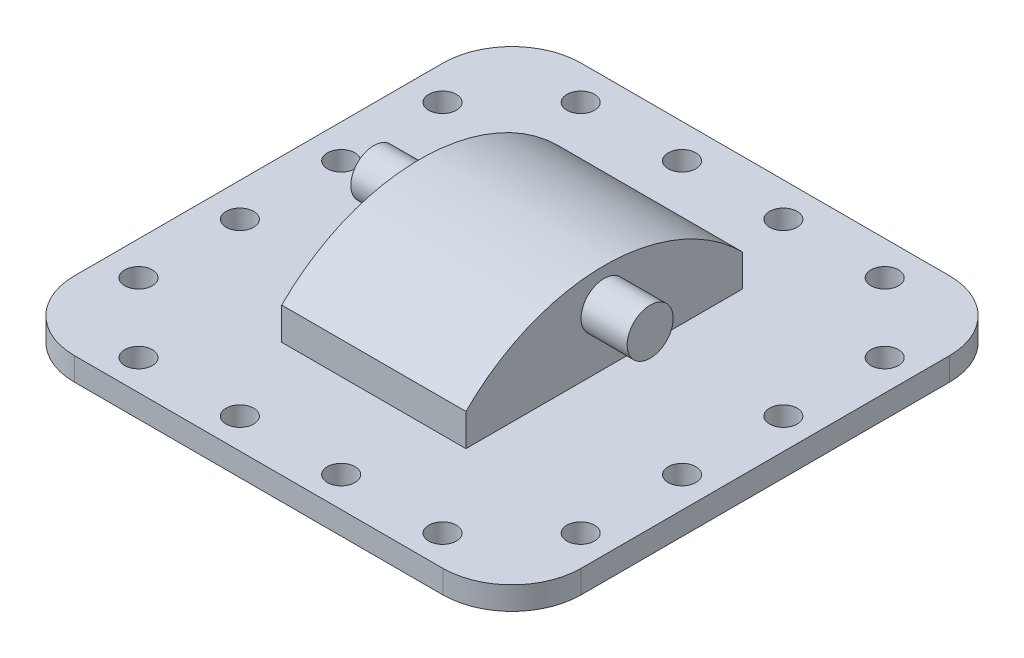
SolidWorks part; units mm, degrees
ref_plane "Front Plane" through (0, 0, 0) normal (0, 0, 1) x (1, 0, 0)
ref_plane "Top Plane" through (0, 0, 0) normal (0, 1, 0) x (1, 0, 0)
ref_plane "Right Plane" through (0, 0, 0) normal (1, 0, 0) x (0, 0, -1)
sketch "Sketch1" plane through (0, 0, 0) normal (0, 1, 0) x (1, 0, 0)
  line L1 (-55, -55) -> (55, -55)
  line L2 (-55, -55) -> (-55, 55)
  line L3 (-55, 55) -> (55, 55)
  line L4 (55, -55) -> (55, 55)
  line L5 (-55, -55) -> (55, 55) construction
  line L6 (-55, 55) -> (55, -55) construction
  point P0 (0, 0)
  dimension "D1" = 110
  dimension "D2" = 110
extrude "Boss-Extrude1" add sketch "Sketch1" along normal blind 5
fillet "Fillet2" radius 15 1 edges at (55, 2.5, -55) type face fillet first side face at (55, 2.5, 0) second side face at (0, 2.5, -55)
fillet "Fillet3" radius 15 1 edges at (-55, 2.5, -55) type face fillet first side face at (-7.5, 2.5, -55) second side face at (-55, 2.5, 0)
fillet "Fillet4" radius 15 1 edges at (-55, 2.5, 55) type face fillet first side face at (-55, 2.5, 7.5) second side face at (0, 2.5, 55)
fillet "Fillet5" radius 15 1 edges at (55, 2.5, 55) type face fillet first side face at (7.5, 2.5, 55) second side face at (55, 2.5, 7.5)
sketch "Sketch2" plane through (0, 5, 0) normal (0, 1, 0) x (1, 0, 0)
  line L1 (-20, -30) -> (20, -30)
  line L2 (-20, -30) -> (-20, 30)
  line L3 (-20, 30) -> (20, 30)
  line L4 (20, -30) -> (20, 30)
  line L5 (-20, -30) -> (20, 30) construction
  line L6 (-20, 30) -> (20, -30) construction
  point P0 (0, 0)
  dimension "D1" = 40
extrude "Boss-Extrude2" add sketch "Sketch2" along normal blind 24
sketch "Sketch4" plane through (20, 0, 0) normal (1, 0, 0) x (0, 0, -1)
  line L0 (-30, 17) -> (30, 17) construction
  line L1 (-30, 29) -> (-30, 5) construction
  line L2 (30, 29) -> (30, 5) construction
  line L3 (0, 17) -> (0, 29) construction
  line L4 (-30, 29) -> (30, 29) construction
  line L5 (0, 29) -> (0, 5) construction
  line L6 (-40, 5) -> (40, 5) construction
  circle A2 centre (0, 17) radius 5
extrude "Boss-Extrude3" add sketch "Sketch4" along normal blind 10 and the other way blind 50
fillet "Fillet6" radius 10 1 edges at (0, 29, 30)
fillet "Fillet7" radius 10 1 edges at (0, 29, -30)
sketch "Sketch5" plane through (0, 0, 0) normal (0, -1, 0) x (1, 0, 0)
  line L0 (55.3347, -39.5816) -> (55.3347, 40.4184)
  line L1 (40.3347, 55.4184) -> (-39.6653, 55.4184)
  line L2 (-54.6653, 40.4184) -> (-54.6653, -39.5816)
  line L3 (-39.6653, -54.5816) -> (40.3347, -54.5816)
  circle A0 centre (48.3347, -10.5816) radius 3
  circle A1 centre (48.3347, 33.4184) radius 3
  circle A2 centre (-47.6653, 11.4184) radius 3
  circle A3 centre (-47.6653, -10.5816) radius 3
  circle A4 centre (-47.6653, -32.5816) radius 3
  circle A5 centre (-32.6653, -47.5816) radius 3
  circle A6 centre (-10.6653, -47.5816) radius 3
  circle A7 centre (11.3347, -47.5816) radius 3
  circle A8 centre (33.3347, -47.5816) radius 3
  circle A9 centre (48.3347, -32.5816) radius 3
  circle A10 centre (48.3347, 11.4184) radius 3
  circle A11 centre (33.3347, 48.4184) radius 3
  circle A12 centre (11.3347, 48.4184) radius 3
  circle A13 centre (-10.6653, 48.4184) radius 3
  circle A14 centre (-32.6653, 48.4184) radius 3
  circle A15 centre (-47.6653, 33.4184) radius 3
  arc A16 (55.3347, 40.4184) -> (40.3347, 55.4184) centre (40.3347, 40.4184) ccw
  arc A17 (-39.6653, 55.4184) -> (-54.6653, 40.4184) centre (-39.6653, 40.4184) ccw
  arc A18 (-54.6653, -39.5816) -> (-39.6653, -54.5816) centre (-39.6653, -39.5816) ccw
  arc A19 (40.3347, -54.5816) -> (55.3347, -39.5816) centre (40.3347, -39.5816) ccw
extrude "Cut-Extrude1" cut sketch "Sketch5" against normal blind 10 contours A1 | A0 | A5 | A4 | A3 | A2 | A13 | A12 | A11 | A10 | A9 | A8 | A7 | A6 | A15 | A14
sketch "Sketch6" plane through (20, 0, 0) normal (1, 0, 0) x (0, 0, -1)
  line L0 (-30, 19) -> (-30, 5) construction
  line L1 (30, 19) -> (30, 5) construction
  line L2 (-20, 29) -> (20, 29) construction
  line L3 (30, 19) -> (30, 12)
  line L4 (-20, 29) -> (20, 29)
  line L5 (-30, 19) -> (-30, 12)
  arc A0 (-30, 12) -> (30, 12) centre (0, -18) cw
  arc A1 (30, 19) -> (20, 29) centre (20, 19) ccw construction
  arc A2 (-20, 29) -> (-30, 19) centre (-20, 19) ccw construction
  arc A3 (30, 19) -> (20, 29) centre (20, 19) ccw
  arc A4 (-20, 29) -> (-30, 19) centre (-20, 19) ccw
extrude "Cut-Extrude2" cut sketch "Sketch6" against normal blind 60
sketch "Sketch7" plane through (0, 5, 0) normal (0, 1, 0) x (1, 0, 0)
  line L0 (-20, 30) -> (20, 30)
  line L1 (20, 30) -> (20, -30)
  line L2 (20, -30) -> (-20, -30)
  line L3 (-20, -30) -> (-20, 30)
split "Split1" bodies to split 105 resulting bodies 106 107 split by face at (48.3347, 5, -13.5816)
